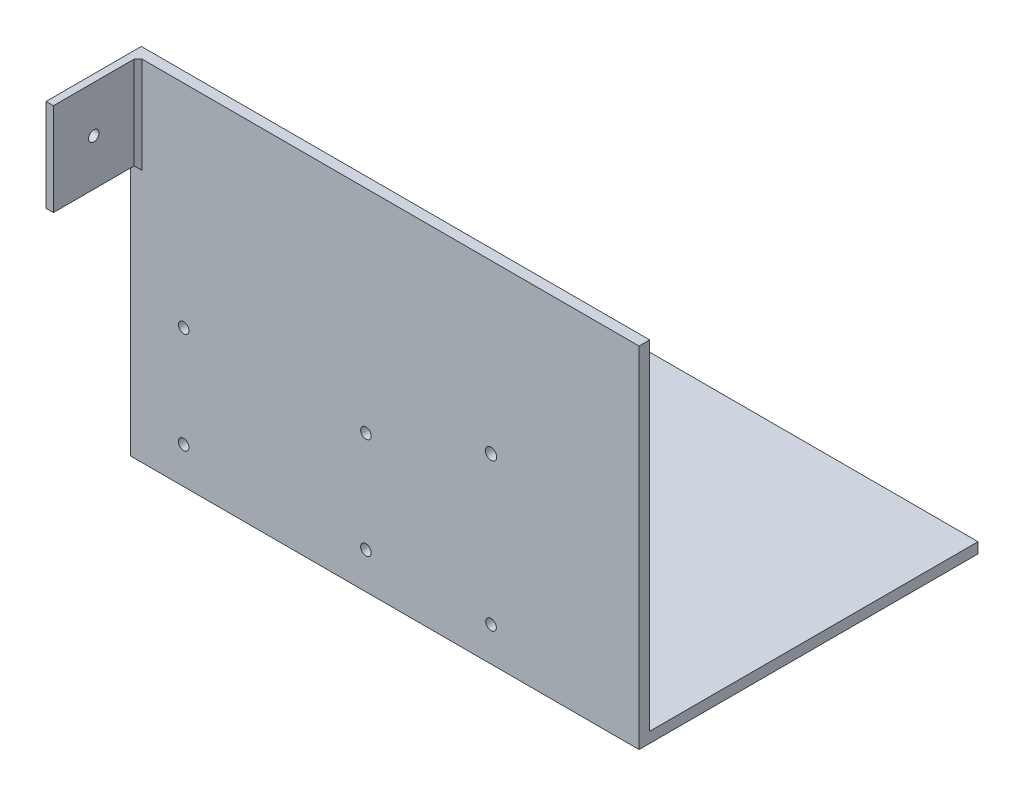
SolidWorks part; units mm, degrees
ref_plane "Front Plane" through (0, 0, 0) normal (0, 0, 1) x (1, 0, 0)
ref_plane "Top Plane" through (0, 0, 0) normal (0, 1, 0) x (1, 0, 0)
ref_plane "Right Plane" through (0, 0, 0) normal (1, 0, 0) x (0, 0, -1)
sketch "Sketch1" plane through (0, 0, 0) normal (0, 1, 0) x (1, 0, 0)
  line L1 (152.4, 101.6) -> (-152.4, 101.6)
  line L2 (152.4, 101.6) -> (152.4, -101.6)
  line L3 (152.4, -101.6) -> (-152.4, -101.6)
  line L4 (-152.4, 101.6) -> (-152.4, -101.6)
  line L5 (152.4, 101.6) -> (-152.4, -101.6) construction
  line L6 (152.4, -101.6) -> (-152.4, 101.6) construction
  point P0 (0, 0)
  dimension "D1" = 304.8
  dimension "D2" = 203.2
extrude "Boss-Extrude1" add sketch "Sketch1" along normal blind 6.35
sketch "Sketch2" plane through (0, 6.35, 0) normal (0, 1, 0) x (1, 0, 0)
  line L0 (152.4, -101.6) -> (152.4, 101.6) construction
  line L6 (-152.4, -101.6) -> (152.4, -101.6)
  line L7 (-152.4, -101.6) -> (-152.4, -95.25)
  line L8 (-152.4, -95.25) -> (152.4, -95.25)
  line L9 (152.4, -101.6) -> (152.4, -95.25)
  dimension "D2" = 6.35
extrude "Boss-Extrude2" add sketch "Sketch2" along normal blind 40.64
sketch "Sketch3" plane through (152.4, 0, 0) normal (1, 0, 0) x (0, 0, -1)
  line L0 (0, 3.4925) -> (0, -3.4925) construction
  line L1 (-101.6, 46.99) -> (-81.1967, 46.99)
  line L2 (-101.6, 46.99) -> (-101.6, 6.35)
  line L3 (-101.6, 6.35) -> (-81.1967, 6.35)
  line L4 (-81.1967, 46.99) -> (-81.1967, 6.35)
  line L5 (101.6, 6.35) -> (81.1967, 6.35)
  line L6 (81.1967, 46.99) -> (81.1967, 6.35)
  line L7 (101.6, 46.99) -> (81.1967, 46.99)
  line L8 (101.6, 46.99) -> (101.6, 6.35)
extrude "Cut-Extrude1" cut sketch "Sketch3" against normal through all
extrude "Boss-Extrude3" add sketch "Sketch2<2>" along normal blind 203.2
sketch "Sketch2<2>" plane through (0, 6.35, 0) normal (0, 1, 0) x (1, 0, 0) same geometry as "Sketch2"
sketch "Sketch9" plane through (0, 0, 0) normal (0, -1, 0) x (1, 0, 0)
  circle A0 centre (63.625, 73.6275) radius 3.175
  circle A1 centre (-11.38, 79.0786) radius 3.175
  circle A3 centre (-120.65, 79.0786) radius 3.175
  circle A4 centre (-120.65, 18.103) radius 3.175
  circle A6 centre (-11.38, 18.103) radius 3.175
extrude "Cut-Extrude2" cut sketch "Sketch9" against normal blind 10.922
sketch "Sketch10" plane through (0, 0, 101.6) normal (0, 0, 1) x (1, 0, 0)
  circle A0 centre (63.625, 109.2241) radius 3.3928
  circle A1 centre (63.625, 20.5557) radius 3.175
  circle A4 centre (-120.65, 82.55) radius 3.175
  circle A5 centre (-120.65, 21.8994) radius 3.175
  circle A6 centre (-11.38, 82.4646) radius 3.175
  circle A7 centre (-11.38, 21.8141) radius 3.175
extrude "Cut-Extrude3" cut sketch "Sketch10" against normal blind 10.922
sketch "Sketch11" plane through (0, 0, 101.6) normal (0, 0, 1) x (1, 0, 0)
  line L1 (-152.4, 209.55) -> (-147.9592, 209.55)
  line L2 (-152.4, 209.55) -> (-152.4, 154.0645)
  line L3 (-152.4, 154.0645) -> (-147.9592, 154.0645)
  line L4 (-147.9592, 209.55) -> (-147.9592, 154.0645)
extrude "Boss-Extrude7" add sketch "Sketch11" along normal blind 50.8
chamfer "Chamfer1" distance 2.38 angle 45 2 edges at (-147.9592, 181.8073, 101.6) (-150.1796, 154.0645, 101.6)
sketch "Sketch12" plane through (0, 0, 0) normal (0, -1, 0) x (1, 0, 0)
  line L1 (-152.4, -101.6) -> (-147.3104, -101.6)
  line L2 (-152.4, -101.6) -> (-152.4, -50.3982)
  line L3 (-152.4, -50.3982) -> (-147.3104, -50.3982)
  line L4 (-147.3104, -101.6) -> (-147.3104, -50.3982)
extrude "Boss-Extrude8" add sketch "Sketch12" along normal blind 50.8
chamfer "Chamfer2" distance 2.38 angle 45 2 edges at (-149.8552, 0, -50.3982) (-147.3104, 0, -75.9991)
sketch "Sketch13" plane through (-147.3104, 0, 0) normal (1, 0, 0) x (0, 0, -1)
  circle A0 centre (75.9991, -26.59) radius 3.175
extrude "Cut-Extrude4" cut sketch "Sketch13" against normal blind 50.8
sketch "Sketch14" plane through (-147.9592, 0, 0) normal (1, 0, 0) x (0, 0, -1)
  circle A0 centre (-128.19, 181.8073) radius 3.175
extrude "Cut-Extrude5" cut sketch "Sketch14" against normal blind 50.8
